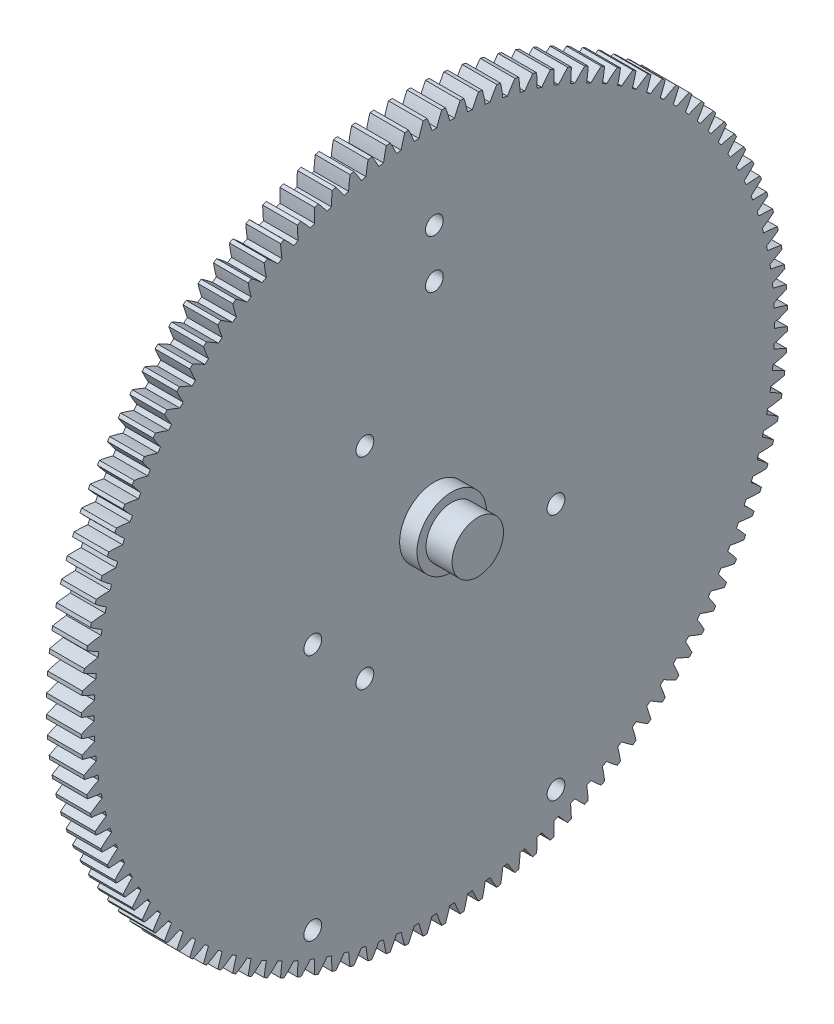
SolidWorks part; units mm, degrees
ref_plane "Plane1" through (0, 0, 0) normal (0, 0, 1) x (1, 0, 0)
ref_plane "Plane2" through (0, 0, 0) normal (0, 1, 0) x (1, 0, 0)
ref_plane "Plane3" through (0, 0, 0) normal (1, 0, 0) x (0, 0, -1)
other "Configuration Table"
sketch "HoldingSke" plane through (0, 0, 0) normal (0, 1, 0) x (1, 0, 0)
  line L0 (0, 0) -> (-152.4, -263.9645)
  line L1 (-15, 0) -> (100, 0) construction
  line L2 (0, 0) -> (-2.1039, 2.3779)
  line L3 (0, 0) -> (-11.863, 4.5341)
  line L4 (0, 0) -> (-4.318, 7.479)
  line L5 (0, 0) -> (-47.5972, -17.7524)
  line L6 (0, 0) -> (-10.5278, -7.1032)
  line L7 (-2.1039, 2.3779) -> (8.8308, 51.9871)
  line L8 (-76.2, 54.61) -> (-54.9402, 54.61)
  line L9 (-71.009, 38.7566) -> (-53.1078, 45.2721)
  line L10 (-76.2, 71.12) -> (104.1128, 71.12)
  line L11 (0, 0) -> (-12.7, 0)
  line L12 (-76.2, 101.6) -> (-76.1147, 101.6)
  line L13 (24.9733, 27.94) -> (52.9518, 28.4284)
  line L14 (24.9733, 27.94) -> (24.9746, 27.94)
  line L15 (24.9733, 27.94) -> (100.4006, 29.5858)
  circle A0 centre (0, 0) radius 9.525
  circle A1 centre (0, 0) radius 38.1
  circle A2 centre (0, 0) radius 38.1
  circle A3 centre (0, 0) radius 9.525
  dimension "MHD" = 76.2
  dimension "Hub_dia" = 76.2
  dimension "Bore" = 19.05
  dimension "MBD" = 19.05
  dimension "Num_teeth" = 120
  dimension "Pitch" = 304.8
  dimension "Overall_len" = 50.8
  dimension "Show_teeth" = 120
  dimension "Thickness" = 12.7
  dimension "OAL" = 50.8001
  dimension "T_dim" = 21.2598
  dimension "Ap" = 20
  dimension "H" = 19.05
  dimension "Pitch_radius" = 180.3128
  dimension "Width" = 12.7
  dimension "Backlash" = 0.0853
  dimension "Addendum_fac" = 1
  dimension "Dedendum_fac" = 1.25
  dimension "Clearance_fac" = 0.25
  dimension "Dedendum_add" = 0.0013
sketch "BasProSke" plane through (0, 0, 0) normal (0, 1, 0) x (1, 0, 0)
  line L0 (-10, 0) -> (60, 0) construction
  line L1 (0, 0) -> (0, 129.1167)
  line L2 (0, 0) -> (12.7, 0)
  line L3 (12.7, 0) -> (12.7, 129.1167)
  line L4 (12.7, 129.1167) -> (0, 129.1167)
  dimension "Thickness" = 12.7
  dimension "Diameter" = 258.2333
revolve "Base-Revolve" add sketch "BasProSke" angle 360 about L0
sketch "TooCutSke" plane through (0, 0, 0) normal (1, 0, 0) x (0, 0, -1)
  line L1 (0, 0) -> (0, 107) construction
  line L2 (0, 0) -> (-1.8117, 126.9871) construction
  line L3 (0, 0) -> (-6.6485, 253.8949) construction
  line L4 (-1.8117, 126.9871) -> (-3.3242, 126.9475) construction
  arc A0 (0.878, 124.3498) -> (-0.878, 124.3498) centre (0, 0) ccw
  arc A1 (2.6872, 129.1141) -> (-2.6872, 129.1141) centre (0, 0) ccw
  circle A2 centre (0, 0) radius 127 construction
  circle A3 centre (0, 0) radius 119.341 construction
  arc A4 (-0.878, 124.3498) -> (-2.6872, 129.1141) centre (-49.2141, 108.7209) ccw
  arc A5 (2.6872, 129.1141) -> (0.878, 124.3498) centre (49.2141, 108.7209) ccw
  dimension "Root_dia" = 248.7058
  dimension "Overcut_dia" = 258.2841
  dimension "Pitch_dia" = 254
  dimension "Base_dia" = 238.6819
  dimension "Flank_rad" = 50.8
  dimension "Half_ang" = 1.5
  dimension "Half_CT" = 1.513
extrude "ToothCut" cut sketch "TooCutSke" along normal through all
fillet "Breaks" [suppressed] radius 0.0423 tangent propagation no
fillet "RootFillets" [suppressed] radius 0.5304
pattern_circular "TeethCuts" count 120 every 3 about axis through (-10, 0, 0) along (1, 0, 0) of "ToothCut", "RootFillets", "Breaks"
sketch "HubNeaOneSke" plane through (0, 0, 0) normal (-1, 0, 0) x (0, 0, 1)
  circle A0 centre (0, 0) radius 38.1
  dimension "Diameter" = 76.2
extrude "HubNearOne" [suppressed] add sketch "HubNeaOneSke" along normal blind 38.1001
sketch "HubNeaBotSke" plane through (0, 0, 0) normal (-1, 0, 0) x (0, 0, 1)
  circle A0 centre (0, 0) radius 38.1
  dimension "Diameter" = 76.2
extrude "HubNearBoth" [suppressed] add sketch "HubNeaBotSke" along normal blind 19.05
ref_plane "FarPln" through (12.7, 0, 0) normal (1, 0, 0) x (0, 0, -1)
sketch "HubFarSke" plane through (12.7, 0, 0) normal (1, 0, 0) x (0, 0, -1)
  circle A0 centre (0, 0) radius 38.1
  dimension "Diameter" = 76.2
extrude "HubFar" [suppressed] add sketch "HubFarSke" along normal blind 19.05
sketch "BorSke" plane through (0, 0, 0) normal (1, 0, 0) x (0, 0, -1)
  circle A0 centre (0, 0) radius 9.525
  dimension "Diameter" = 19.05
extrude "Bore" [suppressed] cut sketch "BorSke" along normal mid plane 101.6001
sketch "KeySke" plane through (0, 0, 0) normal (1, 0, 0) x (0, 0, -1)
  line L0 (-2.3813, 0) -> (-2.3813, 11.7348)
  line L1 (-2.3813, 11.7348) -> (2.3813, 11.7348)
  line L2 (2.3813, 11.7348) -> (2.3813, 0)
  line L3 (0, 0) -> (0, 34) construction
  line L4 (-2.3813, 0) -> (2.3813, 0)
  dimension "Offset" = 11.7348
  dimension "Width" = 4.7625
extrude "Keyway" [suppressed] cut sketch "KeySke" along normal mid plane 101.6001
pattern_circular "Keyway2" [suppressed] count 2 every 90 about axis through (-10, 0, 0) along (1, 0, 0)
sketch "Sketch1" plane through (0, 0, 0) normal (-1, 0, 0) x (0, 0, 1)
  line L0 (0, 0) -> (46.9612, 0) construction
  line L1 (0, 0) -> (0, -76.4863) construction
  circle A2 centre (25.4, 36.83) radius 3.2512
  circle A3 centre (25.4, -36.83) radius 3.2512
  circle A4 centre (0, 93.98) radius 3.2512
  circle A5 centre (0, 76.2) radius 3.2512
  circle A6 centre (44.45, -16.51) radius 3.2512
  circle A7 centre (44.45, -106.934) radius 3.2512
  circle A8 centre (-44.45, -106.934) radius 3.2512
  circle A9 centre (-44.45, -16.51) radius 3.2512
  dimension "D1" = 6.5024
  dimension "D2" = 6.5024
  dimension "D6" = 6.5024
  dimension "D7" = 6.5024
  dimension "D10" = 6.5024
  dimension "D11" = 6.5024
  dimension "D3" = 17.78
  dimension "D4" = 73.66
  dimension "D5" = 25.4
  dimension "D8" = 76.2
  dimension "D9" = 73.66
  dimension "D12" = 90.424
  dimension "D13" = 44.45
  dimension "D14" = 16.51
extrude "Cut-Extrude1" cut sketch "Sketch1" against normal through all
sketch "Sketch2" plane through (12.7, 0, 0) normal (1, 0, 0) x (0, 0, -1)
  circle A0 centre (0, 0) radius 12.7
  dimension "D1" = 25.4
extrude "Boss-Extrude1" add sketch "Sketch2" along normal blind 6.35
sketch "Sketch3" plane through (19.05, 0, 0) normal (1, 0, 0) x (0, 0, -1)
  circle A0 centre (0, 0) radius 9.398
  dimension "D1" = 18.796
extrude "Boss-Extrude2" add sketch "Sketch3" along normal blind 9.525
equation "' \"Pitch@HoldingSke\" = 4"
equation "' \"Num_teeth@HoldingSke\" = 12"
equation "' \"Ap@HoldingSke\" =  20"
equation "' \"Ap@HoldingSke\" = 20"
equation "' \"Width@HoldingSke\" = 0.5"
equation "' \"Hub_dia@HoldingSke\"= 1"
equation "' \"Hub_dia@HoldingSke\" = 1"
equation "' \"Overall_len@HoldingSke\" = 1.0"
equation "' \"Bore@HoldingSke\" = 0.75"
equation "' \"T_dim@HoldingSke\" = 0.85"
equation "' \"Width@KeySke\" = 0.25"
equation "' \"Show_teeth@HoldingSke\" = 13"
equation "' \"Backlash@HoldingSke\" = 0.009"
equation "' \"Addendum_fac@HoldingSke\" = 1.0"
equation "' \"Dedendum_fac@HoldingSke\" = 1.25"
equation "' \"Dedendum_add@HoldingSke\" = 0.00005"
equation "' \"Clearance_fac@HoldingSke\" = 0.25"
equation "' \"Pitch@HoldingSke\" = 0.5"
equation "' \"Num_teeth@HoldingSke\" = 23"
equation "' \"Show_teeth@HoldingSke\" = 23"
equation "' \"Backlash@HoldingSke\" = 0.0375"
equation "\"Overcut_dia@TooCutSke\" = (\"Num_teeth@HoldingSke\" + 2 * \"Addendum_fac@HoldingSke\") / \"Pitch@HoldingSke\" + 0.002"
equation "\"Pitch_dia@TooCutSke\" = \"Num_teeth@HoldingSke\" / \"Pitch@HoldingSke\""
equation "\"Base_dia@TooCutSke\" = \"Num_teeth@HoldingSke\" / \"Pitch@HoldingSke\" * cos((\"Ap@HoldingSke\"  * 3.14159265 / 180))"
equation "\"Root_dia@TooCutSke\" = (\"Num_teeth@HoldingSke\" + 2) / \"Pitch@HoldingSke\" - 2 * (\"Addendum_fac@HoldingSke\" + \"Dedendum_fac@HoldingSke\") / \"Pitch@HoldingSke\" - \"Dedendum_add@HoldingSke\" * 2"
equation "\"Half_ang@TooCutSke\" = 180 / \"Num_teeth@HoldingSke\""
equation "\"Half_CT@TooCutSke\" = \"Num_teeth@HoldingSke\" / \"Pitch@HoldingSke\" * sin((3.14159265 / 2 / \"Num_teeth@HoldingSke\")) / 2 - 7 * \"Backlash@HoldingSke\" / 4"
equation "\"Flank_rad@TooCutSke\" = \"Num_teeth@HoldingSke\" / \"Pitch@HoldingSke\" / 5"
equation "\"Radius@RootFillets\" = \"Clearance_fac@HoldingSke\" / \"Pitch@HoldingSke\" + \"Dedendum_add@HoldingSke\""
equation "\"Break_rad@Breaks\" = 0.02 / \"Pitch@HoldingSke\""
equation "\"Thickness@HoldingSke\" = \"Width@HoldingSke\""
equation "\"OAL@HoldingSke\" = \"Thickness@HoldingSke\""
equation "\"MHD@HoldingSke\" = (\"Num_teeth@HoldingSke\" + 2) / \"Pitch@HoldingSke\" - 2 * (\"Addendum_fac@HoldingSke\" + \"Dedendum_fac@HoldingSke\")  / \"Pitch@HoldingSke\" - \"Dedendum_add@HoldingSke\" * 2"
equation "\"MBD@HoldingSke\" = (\"Num_teeth@HoldingSke\" + 2) / \"Pitch@HoldingSke\" - 2 * (\"Addendum_fac@HoldingSke\" + \"Dedendum_fac@HoldingSke\")  / \"Pitch@HoldingSke\" - \"Dedendum_add@HoldingSke\" * 2 - 0.002"
equation "\"MHD@HoldingSke\" = ((sgn( \"MHD@HoldingSke\" - \"Hub_dia@HoldingSke\" )-1)*( \"MHD@HoldingSke\" - \"Hub_dia@HoldingSke\" ))/-2+ \"Hub_dia@HoldingSke\""
equation "\"MBD@HoldingSke\" = ((sgn( \"MBD@HoldingSke\" - \"Bore@HoldingSke\" )-1)*( \"MBD@HoldingSke\" - \"Bore@HoldingSke\" ))/-2+ \"Bore@HoldingSke\""
equation "\"OAL@HoldingSke\" = ((sgn( \"OAL@HoldingSke\" - \"Overall_len@HoldingSke\" )+1)*( \"OAL@HoldingSke\" - \"Overall_len@HoldingSke\" ))/2 + \"Overall_len@HoldingSke\" + 0.000002"
equation "\"Num_teeth@TeethCuts\" = int( \"Show_teeth@HoldingSke\" ) + 1"
equation "\"Num_teeth@TeethCuts\" = ((sgn( \"Num_teeth@TeethCuts\" - \"Num_teeth@HoldingSke\" )-1)*( \"Num_teeth@TeethCuts\" - \"Num_teeth@HoldingSke\" ))/-2+ \"Num_teeth@HoldingSke\""
equation "\"Num_teeth@TeethCuts\" = ((sgn( \"Num_teeth@TeethCuts\" - 2.0)+1)*( \"Num_teeth@TeethCuts\" - 2.0))/2 +2.0"
equation "\"Angle@TeethCuts\" = 360.0 / \"Num_teeth@HoldingSke\""
equation "\"Diameter@BasProSke\" = (\"Num_teeth@HoldingSke\" + 2 * \"Addendum_fac@HoldingSke\") / \"Pitch@HoldingSke\""
equation "\"Thickness@BasProSke\"  = \"Thickness@HoldingSke\""
equation "' \"Fillet_rad@BasProSke\" =  \"Thickness@HoldingSke\" * 0.05"
equation "' \"Fillet_rad@BasProSke\" = \"Thickness@HoldingSke\" * 0.05"
equation "\"MHD@HoldingSke\" = ((sgn( \"MHD@HoldingSke\" - \"Root_dia@TooCutSke\" )-1)*( \"MHD@HoldingSke\" - \"Root_dia@TooCutSke\" ))/-2+ \"Root_dia@TooCutSke\""
equation "\"Diameter@HubNeaOneSke\" = \"MHD@HoldingSke\""
equation "\"Length@HubNearOne\" = \"OAL@HoldingSke\" - \"Thickness@BasProSke\""
equation "\"Diameter@HubNeaBotSke\" = \"MHD@HoldingSke\""
equation "\"Length@HubNearBoth\" = ( \"OAL@HoldingSke\" - \"Thickness@BasProSke\" ) / 2.0"
equation "\"Thickness@FarPln\" = \"Thickness@BasProSke\""
equation "\"Diameter@HubFarSke\" = \"MHD@HoldingSke\""
equation "\"Length@HubFar\" = ( \"OAL@HoldingSke\" - \"Thickness@BasProSke\" ) / 2.0"
equation "\"Diameter@BorSke\" = \"MBD@HoldingSke\""
equation "\"D1@Bore\" = \"OAL@HoldingSke\" * 2.0"
equation "\"D1@Keyway\" = \"OAL@HoldingSke\" * 2.0"
equation "\"Offset@KeySke\" = \"T_dim@HoldingSke\" - \"MBD@HoldingSke\" / 2.0"
